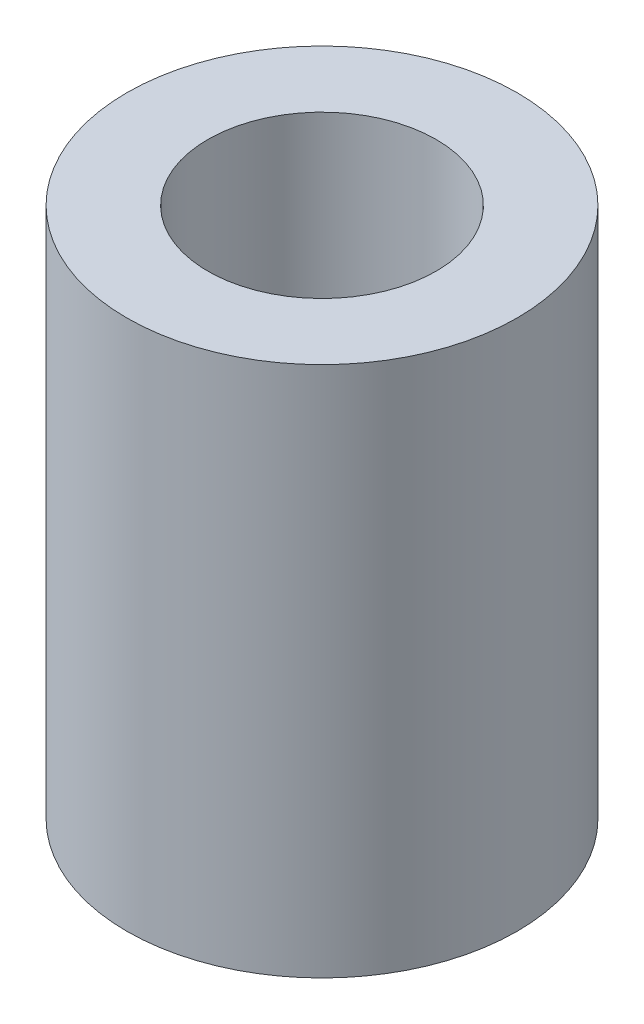
SolidWorks part; units mm, degrees
ref_plane "Front Plane" through (0, 0, 0) normal (0, 0, 1) x (1, 0, 0)
ref_plane "Top Plane" through (0, 0, 0) normal (0, 1, 0) x (1, 0, 0)
ref_plane "Right Plane" through (0, 0, 0) normal (1, 0, 0) x (0, 0, -1)
sketch "Sketch1" plane through (0, 0, 0) normal (0, 1, 0) x (1, 0, 0)
  circle A0 centre (0, 0) radius 2.7991
  circle A1 centre (0, 0) radius 1.6375
  dimension "D1" = 3.275
extrude "Boss-Extrude1" add sketch "Sketch1" along normal blind 7.62
